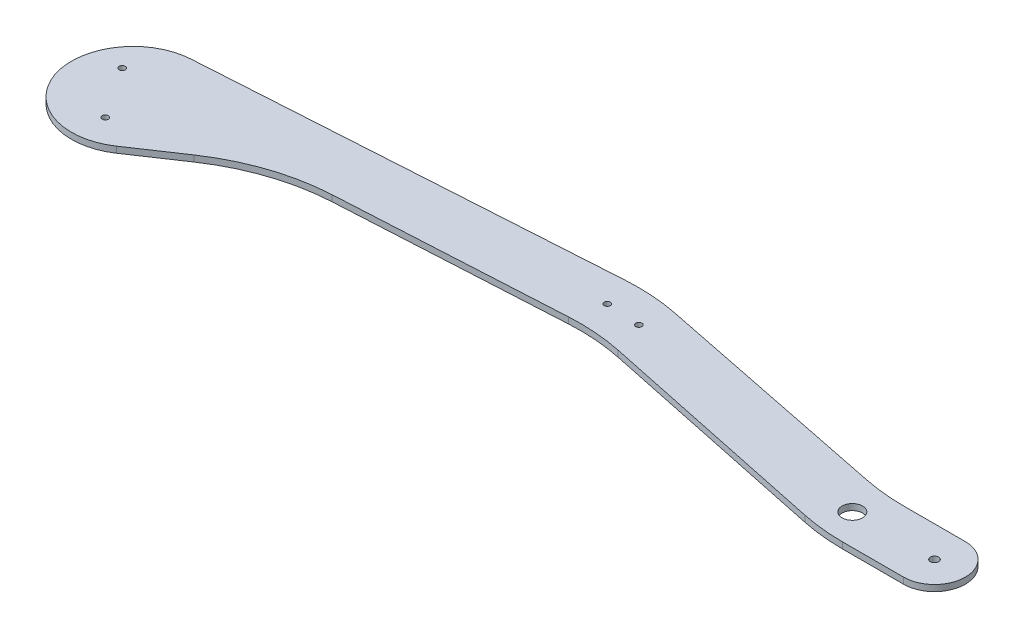
SolidWorks part; units mm, degrees
ref_plane "Front Plane" through (0, 0, 0) normal (0, 0, 1) x (1, 0, 0)
ref_plane "Top Plane" through (0, 0, 0) normal (0, 1, 0) x (1, 0, 0)
ref_plane "Right Plane" through (0, 0, 0) normal (1, 0, 0) x (0, 0, -1)
sketch "Sketch1" plane through (0, 0, 0) normal (0, 1, 0) x (1, 0, 0)
  line L0 (0, 0) -> (-350, 0) construction
  line L1 (0, 0) -> (40, 0) construction
  line L2 (0, 15) -> (40, 15)
  line L3 (0, -15) -> (40, -15)
  line L4 (-351.8754, 29.9413) -> (-333.2857, -24.9125) construction
  line L5 (-139.7849, 43.2259) -> (-4217.6379, -212.1962)
  line L6 (0, 15) -> (-4004.6012, 823.6244)
  line L7 (0, 15) -> (-5.9197, -13.7825) construction
  line L8 (-4217.6379, -212.1962) -> (-138.0533, 13.889)
  line L9 (-4004.6012, 823.6244) -> (-5.9197, -13.7825)
  line L10 (-333.2857, -24.9125) -> (-287.8235, 5.5889)
  line L11 (-5.9197, -13.7825) -> (0, -15)
  circle A0 centre (0, 0) radius 5
  circle A1 centre (-350, 0) radius 30
  circle A2 centre (40, 0) radius 2
  circle A3 centre (0, 0) radius 15
  circle A4 centre (40, 0) radius 15
  dimension "D1" = 10
  dimension "D4" = 4
  dimension "D5" = 60
  dimension "D6" = 30
  dimension "D7" = 165
  dimension "D2" = 350
  dimension "D3" = 40
  dimension "D8" = 165
  dimension "D9" = 135
  dimension "D10" = 150
extrude "Boss-Extrude1" add sketch "Sketch1" along normal blind 1.5 and the other way blind 1.5 contours L8 A1 | A1 L8 | A1 L8 L9 L5 | A1 L10 L8 | A3 L6 L5 L9 | A3 A0 | A4 L2 A3 L3 | A4 A2 region at (-104.3815, 0, -20.1768) region at (20, 0, 0) region at (10.3066, 0, -10.3066) region at (50.3066, 0, -10.3066) region at (-256.3648, 0, -20.0554) region at (-350.7689, 0, -13.8751) region at (-310.7553, 0, 3.5404) region at (-349.359, 0, 11.5664)
fillet "Fillet1" radius 100 5 edges at (0, 0, -15) (-139.7849, 0, -43.2259) (-138.0533, 0, -13.889) (-287.8235, 0, -5.5889) (0, 0, 15)
sketch "Sketch2" plane through (0, 1.5, 0) normal (0, 1, 0) x (1, 0, 0)
  circle A0 centre (-147.3362, 28.0506) radius 1.5
  circle A1 centre (-130.7919, 26.9057) radius 1.5
  circle A2 centre (-364.7467, 9.4158) radius 1.5
  circle A3 centre (-348.0325, -15.4967) radius 1.5
extrude "Cut-Extrude1" cut sketch "Sketch2" against normal blind 10
